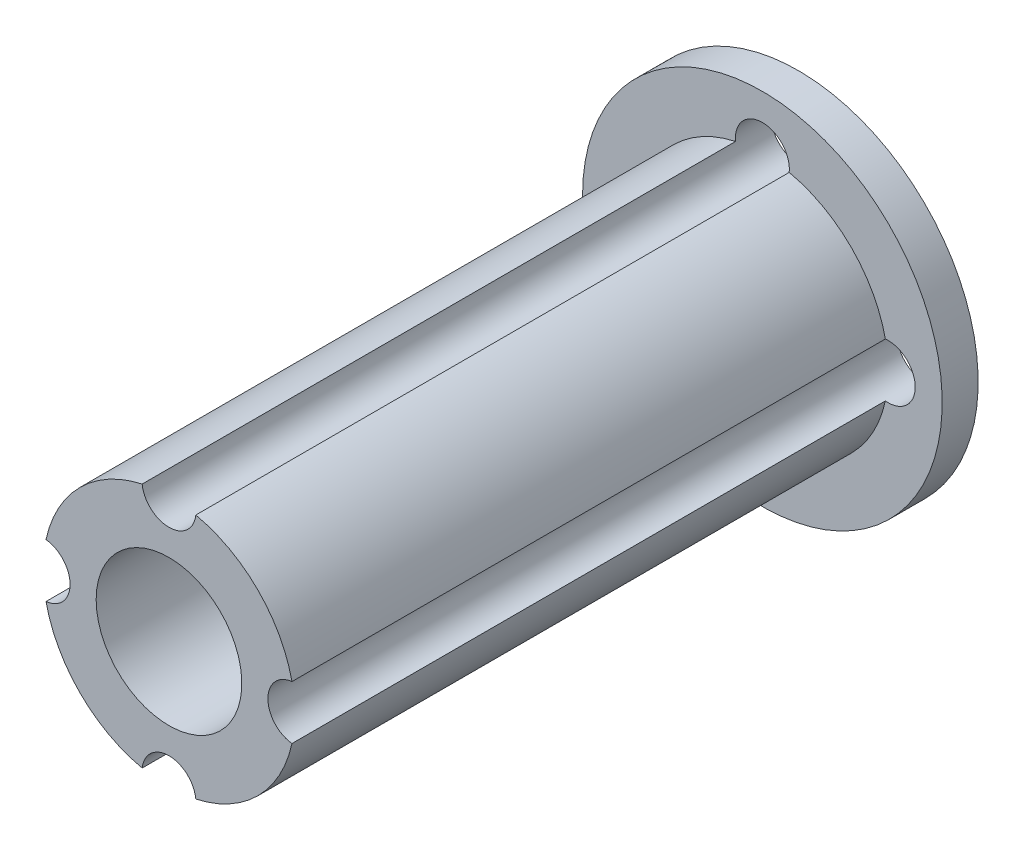
SolidWorks part; units mm, degrees
ref_plane "Front Plane" through (0, 0, 0) normal (0, 0, 1) x (1, 0, 0)
ref_plane "Top Plane" through (0, 0, 0) normal (0, 1, 0) x (1, 0, 0)
ref_plane "Right Plane" through (0, 0, 0) normal (1, 0, 0) x (0, 0, -1)
sketch "Sketch1" plane through (0, 0, 0) normal (0, 0, 1) x (1, 0, 0)
  circle A0 centre (0, 0) radius 4.05
  circle A1 centre (0, 0) radius 7
  circle A3 centre (0, 7) radius 1.5
  circle A4 centre (7, 0) radius 1.5
  circle A5 centre (0, -7) radius 1.5
  circle A7 centre (-7, 0) radius 1.5
extrude "Boss-Extrude5" add sketch "Sketch1" along normal blind 35 contours A1
sketch "Sketch2" plane through (0, 0, 0) normal (0, 0, -1) x (-1, 0, 0)
  circle A0 centre (0, 0) radius 10
extrude "Boss-Extrude7" add sketch "Sketch2" against normal blind 2 contours A0
extrude "Cut-Extrude2" cut sketch "Sketch1<19>" along normal blind 41 contours A1 A7 | A1 A7 | A1 A3 | A1 A3 | A1 A4 | A1 A4 | A1 A5 | A1 A5 | A0 region at (6.3353, 0, 0) region at (7.6068, 0, 0) region at (0, 6.3353, 0) region at (0, 7.6068, 0) region at (0, -7.6068, 0) region at (0, -6.3353, 0) region at (-6.3353, 0, 0) region at (-7.6068, 0, 0)
sketch "Sketch1<19>" plane through (0, 0, 0) normal (0, 0, 1) x (1, 0, 0) same geometry as "Sketch1"
